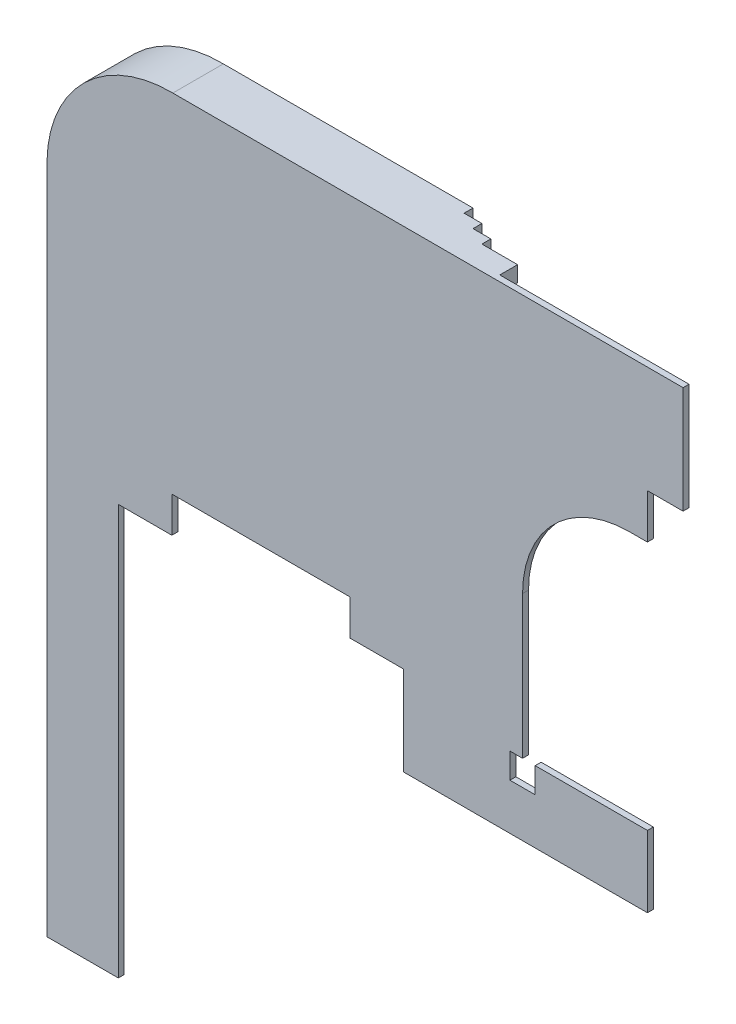
SolidWorks part; units mm, degrees
ref_plane "Front Plane" through (0, 0, 0) normal (0, 0, 1) x (1, 0, 0)
ref_plane "Top Plane" through (0, 0, 0) normal (0, 1, 0) x (1, 0, 0)
ref_plane "Right Plane" through (0, 0, 0) normal (1, 0, 0) x (0, 0, -1)
sketch "Sketch1" plane through (0, 0, 0) normal (0, 0, 1) x (1, 0, 0)
  line L0 (-19250.6646, 20741.7184) -> (-20469.8646, 20741.7184)
  line L1 (-12832.8035, 34305.3184) -> (-9598.6646, 34305.3184)
  line L2 (-9598.6646, 34305.3184) -> (-9598.6646, 32476.5184)
  line L3 (-20469.8646, 27752.1184) -> (-20469.8646, 29166.5122)
  line L4 (-19250.6646, 27752.1184) -> (-20469.8646, 27752.1184)
  line L8 (-19250.6646, 20741.7184) -> (-19250.6646, 27752.1184)
  line L9 (-19250.6646, 27752.1184) -> (-18336.2646, 27752.1184)
  line L10 (-18336.2646, 27752.1184) -> (-18336.2646, 28361.7184)
  line L11 (-18336.2646, 28361.7184) -> (-15288.2646, 28361.7184)
  line L12 (-15288.2646, 28361.7184) -> (-15288.2646, 27752.1184)
  line L13 (-15288.2646, 27752.1184) -> (-14373.8646, 27752.1184)
  line L14 (-14373.8646, 27752.1184) -> (-14373.8646, 26228.1184)
  line L15 (-14373.8646, 26228.1184) -> (-13916.6646, 26228.1184)
  line L24 (-10208.2646, 32476.5184) -> (-10208.2646, 26228.1184)
  line L25 (-12697.4646, 26228.1184) -> (-10208.2646, 26228.1184)
  line L34 (-9598.6646, 32476.5184) -> (-10208.2646, 32476.5184)
  line L42 (-20469.8646, 20741.7184) -> (-20469.8646, 27752.1184)
  line L43 (-12832.8035, 34038.6184) -> (-18348.9693, 34038.6184)
  line L55 (-12697.4646, 26228.1184) -> (-13916.6646, 26228.1184)
  line L56 (-12832.8035, 34038.6184) -> (-12832.8035, 34305.3184)
  line L57 (-20469.8646, 29166.5122) -> (-20202.925, 29166.5122)
  line L58 (-12832.8035, 34305.3184) -> (-18319.2035, 34305.3184)
  line L59 (-20469.8646, 29166.5122) -> (-20469.8646, 32214.5122)
  line L60 (-17739.3693, 33683.0184) -> (-17739.3693, 34038.6184)
  line L61 (-19847.3251, 31574.2184) -> (-20202.925, 31574.076)
  line L62 (-19847.5691, 32183.8183) -> (-19847.3251, 31574.2184)
  line L63 (-18348.9693, 33683.0184) -> (-17739.3693, 33683.0184)
  line L64 (-20202.925, 29166.5122) -> (-20202.925, 32214.5122)
  arc A3 (-18348.9693, 33683.0184) -> (-19847.5691, 32183.8183) centre (-18348.9693, 32184.4184) ccw
  arc A4 (-18348.9693, 34038.6184) -> (-20202.925, 32214.5122) centre (-18348.9693, 32184.4184) ccw
  arc A34 (-18319.2035, 34305.3184) -> (-20469.8646, 32214.5122) centre (-18348.9693, 32184.4184) ccw
  dimension "D50" = 1854.2
  dimension "D51" = 266.7
  dimension "D52" = 3048
  dimension "D55" = 609.6
  dimension "D58" = 355.6
  dimension "D60" = 2121.1089
  dimension "D3" = 1828.8
  dimension "D8" = 1219.2
  dimension "D9" = 7010.4
  dimension "D10" = 914.4
  dimension "D11" = 609.6
  dimension "D12" = 3048
  dimension "D13" = 609.6
  dimension "D14" = 914.4
  dimension "D18" = 457.2
  dimension "D19" = 1524
  dimension "D24" = 2489.2
  dimension "D54" = 5486.4
  dimension "D56" = 609.6
  dimension "D59" = 355.6
extrude "Boss-Extrude1" add sketch "Sketch1" against normal blind 101.6 contours L42 L0 L8 L4 | L63 A3 L62 L61 L64 L57 L3 L4 L9 L10 L11 L12 L13 L14 L15 L55 L25 L24 L34 L2 L1 L56 L43 L60 region at (-19860.2646, 24246.9184, 0) region at (-14656.2733, 30592.1182, 0)
extrude "Boss-Extrude2" add sketch "Sketch1<15>" against normal blind 558.8 contours L43 A4 L64 L61 L62 A3 L63 L60 region at (-20168.0781, 31894.2941, 0)
sketch "Sketch1<15>" plane through (0, 0, 0) normal (0, 0, 1) x (1, 0, 0) same geometry as "Sketch1"
extrude "Boss-Extrude3" add sketch "Sketch1<17>" against normal blind 863.6 contours L58 A34 L59 L57 L64 A4 L43 L56 region at (-20377.8135, 30690.5122, 0)
sketch "Sketch1<17>" plane through (0, 0, 0) normal (0, 0, 1) x (1, 0, 0) same geometry as "Sketch1"
sketch "Sketch3" plane through (0, 34038.6184, 0) normal (0, -1, 0) x (1, 0, 0)
  line L0 (-13747.2035, -558.8) -> (-13747.2035, -711.2)
  line L1 (-12832.8035, -863.6) -> (-12832.8035, -101.6) construction
  line L6 (-12832.8035, -406.4) -> (-13442.4035, -406.4)
  line L7 (-13442.4035, -406.4) -> (-13442.4035, -558.8)
  line L8 (-13442.4035, -558.8) -> (-13747.2035, -558.8)
  line L9 (-14052.0035, -711.2) -> (-14052.0035, -863.6)
  line L10 (-12832.8035, -863.6) -> (-18348.9693, -863.6) construction
  line L11 (-14052.0035, -863.6) -> (-12832.8035, -863.6)
  line L12 (-12832.8035, -863.6) -> (-12832.8035, -406.4)
  line L13 (-13747.2035, -711.2) -> (-14052.0035, -711.2)
  dimension "D6" = 609.6
  dimension "D7" = 152.4
extrude "Cut-Extrude1" cut sketch "Sketch3" against normal through all
sketch "Sketch4" plane through (-20202.925, 0, 0) normal (1, 0, 0) x (0, 0, -1)
  line L0 (863.6, 29166.5122) -> (406.4, 29166.5122)
  line L1 (863.6, 29166.5122) -> (101.6, 29166.5122) construction
  line L2 (863.6, 29166.5122) -> (863.6, 30080.9122)
  line L4 (406.4, 29166.5122) -> (406.4, 29776.1122)
  line L6 (406.4, 29776.1122) -> (558.8, 29776.1122)
  line L7 (558.8, 29776.1122) -> (558.8, 30080.9122)
  line L8 (558.8, 30080.9122) -> (711.2, 30080.9122)
  line L9 (711.2, 30080.9122) -> (711.2, 30385.7122)
  line L10 (711.2, 30385.7122) -> (863.6, 30385.7122)
  line L11 (863.6, 29166.5122) -> (863.6, 32214.5122) construction
  line L12 (863.6, 30385.7122) -> (863.6, 30080.9122)
  dimension "D1" = 152.4
  dimension "D2" = 152.4
  dimension "D3" = 609.6
  dimension "D4" = 304.8
  dimension "D5" = 304.8
  dimension "D6" = 152.4
extrude "Cut-Extrude2" cut sketch "Sketch4" against normal through all
sketch "Sketch5" plane through (0, 0, -101.6) normal (0, 0, -1) x (-1, 0, 0)
  line L7 (10208.2646, 32476.5184) -> (10208.2646, 26228.1184) construction
  line L8 (10208.2646, 27447.3184) -> (12341.8646, 27447.3184)
  line L9 (14373.8646, 26228.1184) -> (10208.2646, 26228.1184) construction
  line L10 (10208.2646, 31714.5184) -> (10208.2646, 27447.3184)
  line L11 (10208.2646, 31714.5184) -> (10513.0646, 31714.5184)
  line L12 (12341.8646, 29885.7184) -> (12341.8646, 27447.3184)
  arc A0 (10513.0646, 31714.5184) -> (12341.8646, 29885.7184) centre (10513.0646, 29885.7184) cw
  point P20 (0, 0)
  point P24 (0, 0)
  dimension "D3" = 1828.8
  dimension "D1" = 2133.6
  dimension "D2" = 1219.2
  dimension "D4" = 4267.2
extrude "Cut-Extrude3" cut sketch "Sketch5" against normal through all
sketch "Sketch6" plane through (0, 0, -101.6) normal (0, 0, -1) x (-1, 0, 0)
  line L1 (12125.9646, 27015.5184) -> (12557.7646, 27015.5184)
  line L2 (12125.9646, 27015.5184) -> (12125.9646, 27447.3184)
  line L3 (12125.9646, 27447.3184) -> (12557.7646, 27447.3184)
  line L4 (12557.7646, 27015.5184) -> (12557.7646, 27447.3184)
  point P4 (12341.8646, 27447.3184)
  dimension "D1" = 431.8
  dimension "D2" = 431.8
extrude "Cut-Extrude4" cut sketch "Sketch6" against normal through all
sketch "Sketch7" plane through (0, 0, -101.6) normal (0, 0, -1) x (-1, 0, 0)
  line L1 (19250.6646, 27752.1184) -> (20469.8646, 27752.1184)
  line L2 (19250.6646, 27752.1184) -> (19250.6646, 20741.7184)
  line L3 (19250.6646, 20741.7184) -> (20469.8646, 20741.7184)
  line L4 (20469.8646, 27752.1184) -> (20469.8646, 20741.7184)
extrude "Cut-Extrude5" cut sketch "Sketch7" against normal blind 0.254
